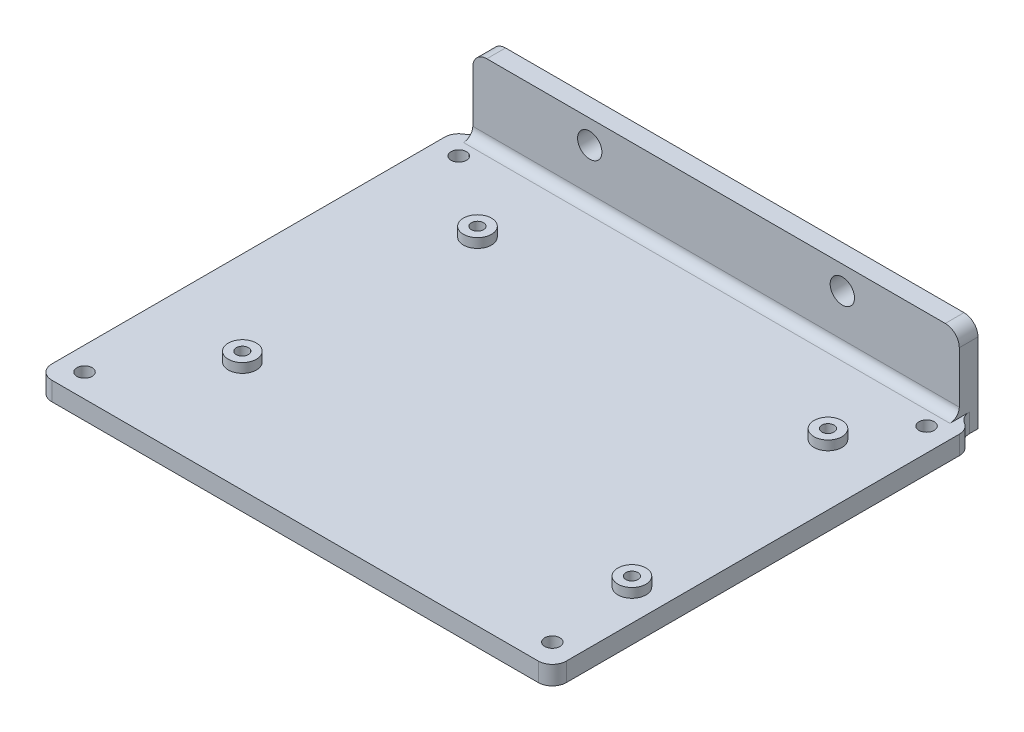
SolidWorks part; units mm, degrees
ref_plane "Front Plane" through (0, 0, 0) normal (0, 0, 1) x (1, 0, 0)
ref_plane "Top Plane" through (0, 0, 0) normal (0, 1, 0) x (1, 0, 0)
ref_plane "Right Plane" through (0, 0, 0) normal (1, 0, 0) x (0, 0, -1)
sketch "Sketch1" plane through (0, 0, 0) normal (0, 1, 0) x (1, 0, 0)
  line L1 (3, 0) -> (107, 0)
  line L2 (0, 3) -> (0, 87)
  line L3 (3, 90) -> (107, 90)
  line L4 (110, 3) -> (110, 87)
  arc A0 (0, 3) -> (3, 0) centre (3, 3) ccw
  arc A1 (107, 0) -> (110, 3) centre (107, 3) ccw
  arc A2 (110, 87) -> (107, 90) centre (107, 87) ccw
  arc A3 (3, 90) -> (0, 87) centre (3, 87) ccw
  point P7 (0, 0)
  point P10 (110, 0)
  point P15 (0, 90)
  dimension "D3" = 3
  dimension "D1" = 90
  dimension "D2" = 110
extrude "Boss-Extrude1" add sketch "Sketch1" along normal blind 4
sketch "Sketch2" plane through (0, 4, 0) normal (0, 1, 0) x (1, 0, 0)
  line L0 (0, 87) -> (0, 3) construction
  line L1 (22, 72) -> (96.93, 72) construction
  line L2 (22, 72) -> (22, 23.74) construction
  line L3 (22, 23.74) -> (103.28, 23.74) construction
  line L4 (96.93, 72) -> (103.28, 23.74) construction
  line L5 (107, 90) -> (3, 90) construction
  line L6 (22, 23.74) -> (20, 23.74) construction
  circle A0 centre (22, 72) radius 3
  circle A2 centre (103.28, 23.74) radius 3
  circle A3 centre (96.93, 72) radius 3
  circle A4 centre (20, 23.74) radius 3
  dimension "D1" = 6
  dimension "D2" = 74.93
  dimension "D3" = 22
  dimension "D4" = 48.26
  dimension "D5" = 81.28
  dimension "D6" = 18
  dimension "D7" = 2
extrude "Boss-Extrude2" add sketch "Sketch2" along normal blind 2
sketch "Sketch3" plane through (0, 6, 0) normal (0, 1, 0) x (1, 0, 0)
  circle A0 centre (22, 72) radius 1.3
  circle A1 centre (96.93, 72) radius 1.3
  circle A2 centre (103.28, 23.74) radius 1.3
  circle A3 centre (20, 23.74) radius 1.3
  dimension "D1" = 2.6
extrude "Cut-Extrude1" cut sketch "Sketch3" against normal blind 6
sketch "Sketch4" plane through (0, 0, -90) normal (0, 0, -1) x (-1, 0, 0)
  line L0 (-3, 4) -> (-3, 0) construction
  line L1 (-107, 0) -> (-3, 0)
  line L2 (-107, 0) -> (-107, 17)
  line L3 (-104, 20) -> (-6, 20)
  line L4 (-3, 0) -> (-3, 17)
  line L6 (-3, 15) -> (-107, 15) construction
  arc A0 (-3, 17) -> (-6, 20) centre (-6, 17) ccw
  arc A1 (-104, 20) -> (-107, 17) centre (-104, 17) ccw
  circle A2 centre (-82, 15) radius 2.6
  circle A3 centre (-28, 15) radius 2.6
  point P11 (-107, 20)
  dimension "D2" = 3
  dimension "D6" = 5.2
  dimension "D1" = 20
  dimension "D3" = 5
  dimension "D4" = 25
  dimension "D5" = 25
extrude "Boss-Extrude3" add sketch "Sketch4" along normal blind 4
fillet "Fillet1" radius 3 2 edges at (107, 2, -90) (3, 2, -90)
fillet "Fillet2" radius 2 1 edges at (55, 4, -90)
sketch "Sketch5" plane through (0, 4, 0) normal (0, 1, 0) x (1, 0, 0)
  line L0 (3, 90) -> (107, 90) construction
  line L1 (5, 85) -> (105, 85) construction
  line L2 (5, 85) -> (5, 5) construction
  line L3 (5, 5) -> (105, 5) construction
  line L4 (105, 85) -> (105, 5) construction
  line L5 (3, 0) -> (107, 0) construction
  line L6 (0, 87) -> (0, 3) construction
  line L7 (110, 3) -> (110, 87) construction
  circle A0 centre (5, 85) radius 1.625
  circle A1 centre (105, 85) radius 1.625
  circle A2 centre (105, 5) radius 1.625
  circle A3 centre (5, 5) radius 1.625
  dimension "D7" = 3.25
  dimension "D1" = 5
  dimension "D2" = 5
  dimension "D3" = 5
  dimension "D4" = 5
  dimension "D5" = 80
  dimension "D6" = 100
extrude "Cut-Extrude2" cut sketch "Sketch5" against normal blind 10
